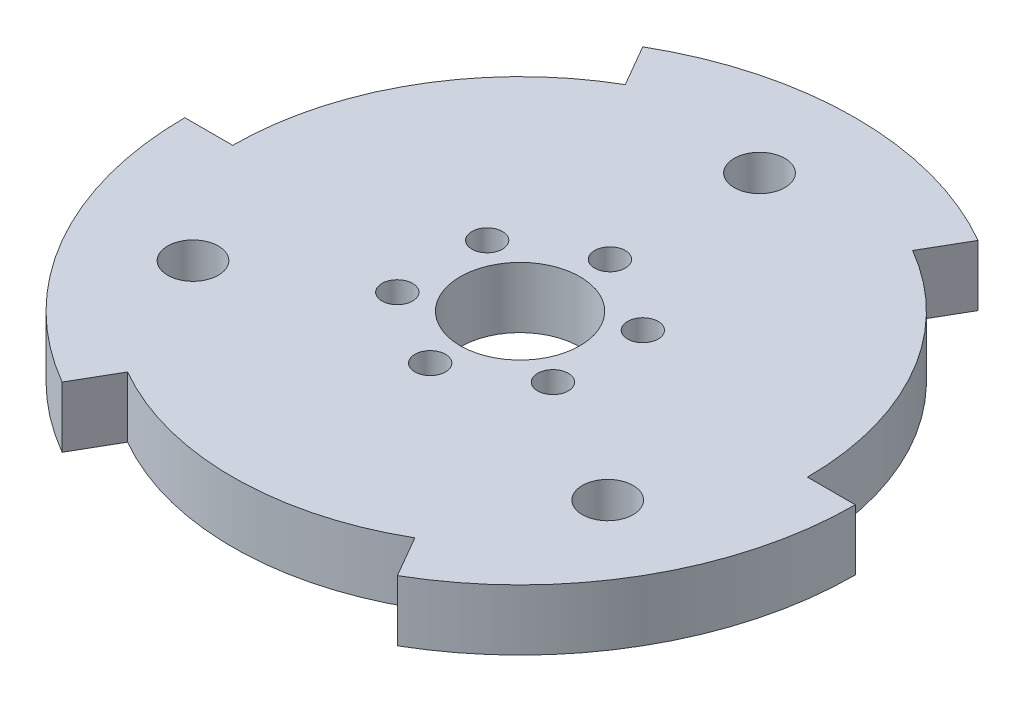
SolidWorks part; units mm, degrees
ref_plane "Front Plane" through (0, 0, 0) normal (0, 0, 1) x (1, 0, 0)
ref_plane "Top Plane" through (0, 0, 0) normal (0, 1, 0) x (1, 0, 0)
ref_plane "Right Plane" through (0, 0, 0) normal (1, 0, 0) x (0, 0, -1)
sketch "Baseplate Sketch" plane through (0, 0, 0) normal (0, 1, 0) x (1, 0, 0)
  line L0 (0, 0) -> (0, 61.4504) construction
  line L1 (-17.5, 30.3109) -> (-15, 25.9808)
  line L2 (17.5, 30.3109) -> (15, 25.9808)
  line L3 (-17.5, 30.3109) -> (-21.8301, 27.8109) construction
  line L4 (17.5, 30.3109) -> (13.1699, 32.8109) construction
  line L5 (17.5, -30.3109) -> (15, -25.9808)
  line L6 (35, 0) -> (30, 0)
  line L7 (-35, 0) -> (-30, 0)
  line L8 (-17.5, -30.3109) -> (-15, -25.9808)
  circle A0 centre (0, 0) radius 30
  circle A1 centre (0, 0) radius 6.25
  arc A2 (-17.5, 30.3109) -> (17.5, 30.3109) centre (0, 0) cw
  arc A3 (35, 0) -> (17.5, -30.3109) centre (0, 0) cw
  arc A4 (-17.5, -30.3109) -> (-35, 0) centre (0, 0) cw
  circle A5 centre (0, 25) radius 2.65
  circle A6 centre (21.6506, -12.5) radius 2.65
  circle A7 centre (-21.6506, -12.5) radius 2.65
  point P15 (0, 35)
  point P25 (0, 0)
  point P31 (0, 0)
  dimension "D1" = 60
  dimension "D2" = 12.5
  dimension "D3" = 35
  dimension "D4" = 90
  dimension "D5" = 5
  dimension "D12" = 5.3
  dimension "D6" = 5
  dimension "D7" = 90
  dimension "D8" = 60
  dimension "D9" = 5
  dimension "D10" = 5
  dimension "D14" = 25
  dimension "D11" = 3
  dimension "D13" = 3
extrude "Boss-Extrude1" add sketch "Baseplate Sketch" along normal blind 6.35 contours A4 L8 A0 L7 | A3 L6 A0 L5 | A2 L1 A0 L2 | A0 | A1 | A6 | A7 | A5 region at (0, 0, -31.0964) region at (-26.9303, 0, 15.5482) region at (26.9303, 0, 15.5482)
ref_plane "Plane1" [suppressed] through (0, 0, 40) normal (0, 0, 1) x (1, 0, 0)
sketch "Sketch2" [suppressed] plane through (0, 0, 40) normal (0, 0, 1) x (1, 0, 0)
  line L0 (0, 6.35) -> (0, 0) construction
  line L4 (15, 6.35) -> (-15, 6.35)
  line L5 (-15, 6.35) -> (-15, 0)
  line L6 (-15, 0) -> (15, 0)
  line L7 (15, 0) -> (15, 6.35)
  line L8 (15, 6.35) -> (-15, 6.35) construction
  line L9 (-15, 6.35) -> (-15, 0) construction
  line L10 (-15, 0) -> (15, 0) construction
  line L11 (15, 0) -> (15, 6.35) construction
  circle A0 centre (0, 3.175) radius 2.25
  dimension "D1" = 0
  dimension "D2" = 4.5
extrude "Cut-Extrude1" [suppressed] cut sketch "Sketch2" against normal blind 25
pattern_circular "CirPattern1" [suppressed] count 3 over 360 of bodies 102
sketch "Sketch3" plane through (0, 6.35, 0) normal (0, 1, 0) x (1, 0, 0)
  circle A2 centre (-8.1276, -4.6925) radius 1.6
  circle A5 centre (0, -9.385) radius 1.6
  circle A6 centre (-8.1276, 4.6925) radius 1.6
  circle A7 centre (0, 9.385) radius 1.6
  circle A8 centre (8.1276, 4.6925) radius 1.6
  circle A9 centre (8.1276, -4.6925) radius 1.6
  point P14 (0, 0)
  dimension "D1" = 3.2
  dimension "D2" = 9.385
  dimension "D3" = 9.385
extrude "Cut-Extrude2" cut sketch "Sketch3" against normal up to surface (6.35 mm away) contours A5 | A2 | A6 | A7 | A8 | A9 region at (-8.1276, 6.35, 4.6925) region at (0, 6.35, 9.385) region at (-8.1276, 6.35, -4.6925) region at (0, 6.35, -9.385) region at (8.1276, 6.35, -4.6925) region at (8.1276, 6.35, 4.6925) up to face at (0, 0, 0)
